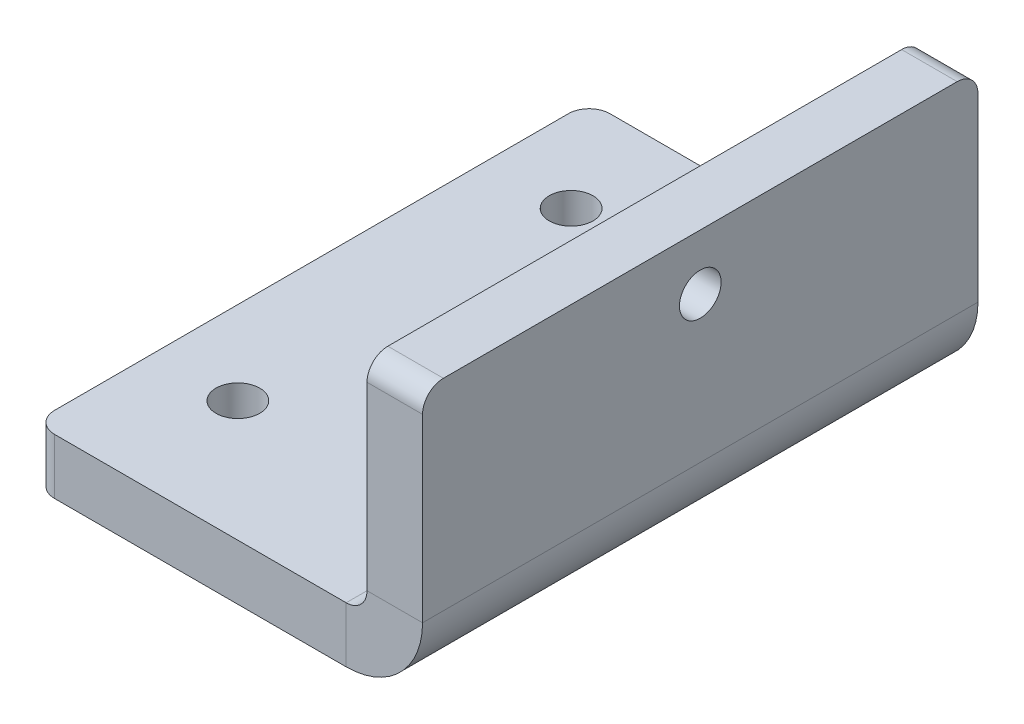
SolidWorks part; units mm, degrees
note: The reader was unsure of these and kept them because the rebuilt part matched: bend radius of "BaseBend1".
ref_plane "Front Plane" through (0, 0, 0) normal (0, 0, 1) x (1, 0, 0)
ref_plane "Top Plane" through (0, 0, 0) normal (0, 1, 0) x (1, 0, 0)
ref_plane "Right Plane" through (0, 0, 0) normal (1, 0, 0) x (0, 0, -1)
sketch "Sketch1" plane through (0, 0, 0) normal (0, 0, 1) x (1, 0, 0)
  line L0 (-48, 0) -> (0, 0)
  line L1 (0, 0) -> (0, 32)
  dimension "D1" = 48
  dimension "D2" = 32
base flange "Base-Flange1" sketch "Sketch1" end condition mid plane depth 80 reverse direction no thickness 8 reverse thickness direction no bend radius 3
bend "BaseBend1" bend radius 3 bend angle 90 parameters "D5"=1
fillet "Fillet1" radius 3 4 edges at (-48, -4, 40) (-48, -4, -40) (4, 32, -40) (4, 32, 40)
sketch "Sketch6" plane through (0, 0, 0) normal (0, 1, 0) x (1, 0, 0)
  line L0 (-48, -37) -> (-48, 37) construction
  line L1 (-36, 25.3977) -> (-36, -22.6023) construction
  circle A0 centre (-36, 25.3977) radius 3.15
  circle A1 centre (-36, -22.6023) radius 3.15
  dimension "D2" = 6.3
  dimension "D1" = 12
  dimension "D3" = 48
extrude "Cut-Extrude1" cut sketch "Sketch6" against normal blind 10 normal cut yes
sketch "Sketch7" plane through (0, 0, 0) normal (-1, 0, 0) x (0, 0, 1)
  line L0 (0, 0) -> (0, 32) construction
  line L1 (37, 32) -> (-37, 32) construction
  circle A0 centre (0, 24) radius 3
  dimension "D1" = 6
  dimension "D2" = 8
extrude "Cut-Extrude2" cut sketch "Sketch7" against normal blind 10 normal cut yes
sketch "Bend-Lines1" [suppressed] plane through (0, 0, 0) normal (0, 1, 0) x (1, 0, 0)
sketch "Bounding-Box1" [suppressed] plane through (0, 0, 0) normal (0, 1, 0) x (1, 0, 0)
sheet metal parameters "Sheet-Metal1" thickness 8 parameters "D1"=3
flat pattern "Flat-Pattern1" [suppressed]
sketch "Bend-Lines2" plane through (0, 0, 0) normal (0, 1, 0) x (1, 0, 0)
  line L0 (1.7438, 40) -> (1.7438, -40) construction
  line L1 (1.7438, 40) -> (1.7438, -40) construction
sketch3d "Bounding-Box2" [suppressed]
  line L0 (0, 0, 0) -> (83.4876, 0, 0) construction
  line L1 (0, 80, 0) -> (83.4876, 80, 0) construction
  line L2 (0, 0, 0) -> (0, 80, 0) construction
  line L3 (83.4876, 0, 0) -> (83.4876, 80, 0) construction
bend of the flat pattern "Flatten-<BaseBend1>1"
sheet metal parameters "Sheet-Metal2" thickness 8 parameters "D1"=3
flat pattern "Flat-Pattern1"
sketch "Bend-Lines2" plane through (0, 0, 0) normal (0, 1, 0) x (1, 0, 0)
  line L0 (1.7438, 40) -> (1.7438, -40) construction
  line L1 (1.7438, 40) -> (1.7438, -40) construction
sketch3d "Bounding-Box2" [suppressed]
  line L0 (0, 0, 0) -> (83.4876, 0, 0) construction
  line L1 (0, 80, 0) -> (83.4876, 80, 0) construction
  line L2 (0, 0, 0) -> (0, 80, 0) construction
  line L3 (83.4876, 0, 0) -> (83.4876, 80, 0) construction
bend of the flat pattern "Flatten-<BaseBend1>1"
sheet metal parameters "Sheet-Metal3" thickness 8 parameters "D1"=3
flat pattern "Flat-Pattern1"
sketch "Bend-Lines2" plane through (0, 0, 0) normal (0, 1, 0) x (1, 0, 0)
  line L0 (1.7438, 40) -> (1.7438, -40) construction
  line L1 (1.7438, 40) -> (1.7438, -40) construction
sketch3d "Bounding-Box2" [suppressed]
  line L0 (0, 0, 0) -> (83.4876, 0, 0) construction
  line L1 (0, 80, 0) -> (83.4876, 80, 0) construction
  line L2 (0, 0, 0) -> (0, 80, 0) construction
  line L3 (83.4876, 0, 0) -> (83.4876, 80, 0) construction
bend of the flat pattern "Flatten-<BaseBend1>1"
